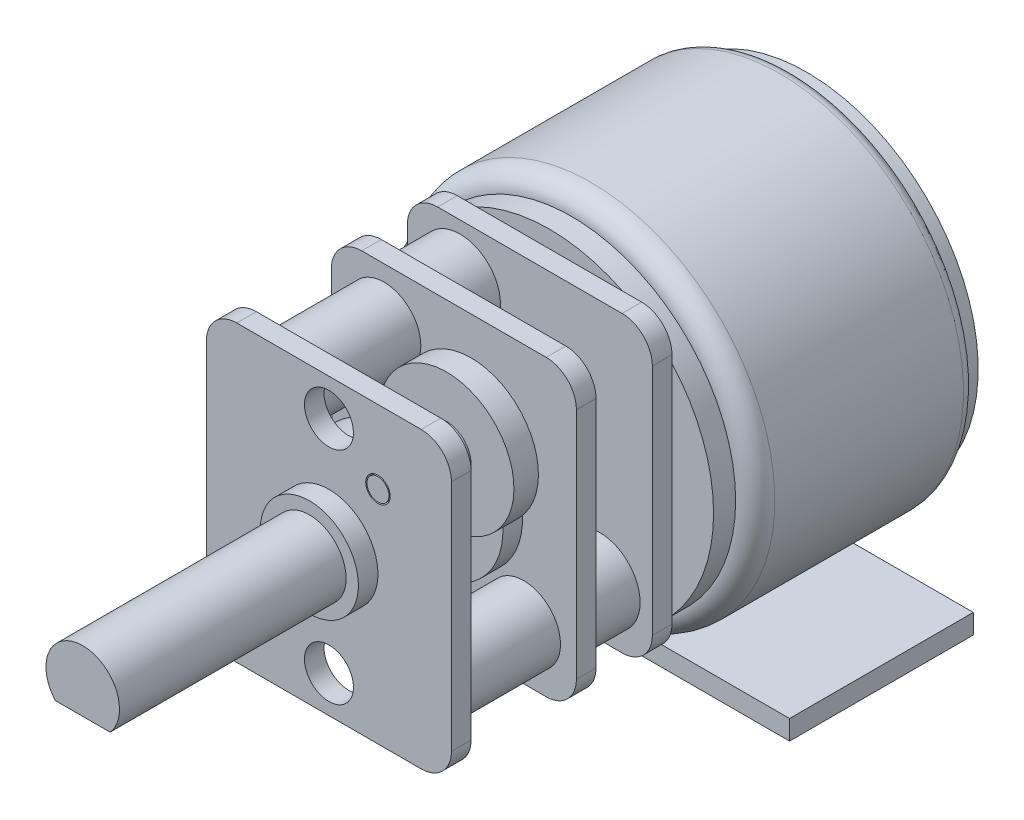
SolidWorks part; units mm, degrees
ref_plane "Front" through (0, 0, 0) normal (0, 0, 1) x (1, 0, 0)
ref_plane "Top" through (0, 0, 0) normal (0, 1, 0) x (1, 0, 0)
ref_plane "Right" through (0, 0, 0) normal (1, 0, 0) x (0, 0, -1)
sketch "Эскиз1" plane through (0, 0, 0) normal (0, 1, 0) x (1, 0, 0)
  line L0 (0, 0) -> (0, -39.2335) construction
  line L1 (0, 0) -> (-0.5, 0)
  line L3 (-0.75, -0.5) -> (-3, -0.5)
  line L4 (-3, -0.5) -> (-3, -1.5)
  line L5 (-3, -1.5) -> (-7, -1.5)
  line L6 (-7, -1.5) -> (-7, -2.1)
  line L8 (-7.5, -2.6) -> (-7.5, -10.3)
  line L10 (-6.7, -11.1) -> (-6.7, -12)
  line L11 (-6.7, -12) -> (-0.75, -12)
  line L12 (0, -12) -> (0, 0)
  line L14 (-7, -2.1) -> (-7, -2.6) construction
  line L15 (-6.7, -11.1) -> (-6.7, -10.3) construction
  line L16 (-6.7, -11.1) -> (-7.5, -11.1) construction
  line L18 (0, -21) -> (-2, -21)
  line L19 (-2, -21) -> (-2, -21.8)
  line L20 (-2, -21.8) -> (-1.5, -21.8)
  line L21 (-1.5, -21.8) -> (-1.5, -31.05)
  line L22 (-1.5, -31.05) -> (0, -31.05)
  line L24 (0, -21) -> (0, -31.05)
  line L25 (-0.75, -12) -> (-0.75, -13.75) construction
  line L26 (0, -14) -> (-0.5, -14) construction
  line L27 (-0.75, -0.5) -> (-0.75, -0.25)
  line L28 (0, -12) -> (-0.75, -12)
  arc A0 (-7, -2.1) -> (-7.5, -2.6) centre (-7, -2.6) ccw
  arc A1 (-7.5, -10.3) -> (-6.7, -11.1) centre (-6.7, -10.3) ccw
  arc A2 (-0.75, -13.75) -> (-0.5, -14) centre (-0.5, -13.75) ccw construction
  arc A3 (-0.5, 0) -> (-0.75, -0.25) centre (-0.5, -0.25) ccw
  dimension "D1" = 6
  dimension "D7" = 0.9
  dimension "D10" = 10.5
  dimension "D16" = 2
  dimension "D4" = 0.5
  dimension "D5" = 0.25
  dimension "D2" = 15
  dimension "D3" = 1
  dimension "D6" = 0.6
  dimension "D8" = 14
  dimension "D9" = 13.4
  dimension "D11" = 19.5
  dimension "D12" = 4
  dimension "D13" = 0.8
  dimension "D14" = 9.25
  dimension "D15" = 3
  dimension "D17" = 1.5
revolve "Motor" add sketch "Эскиз1" angle 360 about L0
sketch "Эскиз2" plane through (0, 0, 31.05) normal (0, 0, 1) x (1, 0, 0)
  line L0 (-1.118, -1) -> (1.118, -1)
  line L1 (-1.6853, 1.5) -> (1.9295, 1.5) construction
  arc A0 (1.118, -1) -> (-1.118, -1) centre (0, 0) ccw
  circle A1 centre (0, 0) radius 1.5 construction
  dimension "D1" = 2.5
extrude "Вырез-Вытянуть2" cut sketch "Эскиз2" against normal up to surface (9.25 mm away) flip side to cut up to face at (-1.5, 0, 21.8)
sketch "Эскиз7" plane through (0, 0, 12) normal (0, 0, 1) x (1, 0, 0)
  line L1 (3.7627, 6) -> (-3.7627, 6)
  line L2 (5, 4.7627) -> (5, -4.7627)
  line L3 (3.7627, -6) -> (-3.7627, -6)
  line L4 (-5, 4.7627) -> (-5, -4.7627)
  line L5 (5, 6) -> (-5, -6) construction
  line L6 (5, -6) -> (-5, 6) construction
  arc A0 (-3.7627, 6) -> (-5, 4.7627) centre (-3.7627, 4.7627) ccw
  arc A1 (-5, -4.7627) -> (-3.7627, -6) centre (-3.7627, -4.7627) ccw
  arc A2 (3.7627, -6) -> (5, -4.7627) centre (3.7627, -4.7627) ccw
  arc A3 (5, 4.7627) -> (3.7627, 6) centre (3.7627, 4.7627) ccw
  point P0 (0, 0)
  point P18 (4.6376, -5.6376)
  point P19 (-4.6376, 5.6376)
  point P20 (0, 0)
  dimension "D3" = 14.6
  dimension "D1" = 10
  dimension "D2" = 12
extrude "Бобышка-Вытянуть5" add sketch "Эскиз7" along normal blind 0.8
sketch "Эскиз8" plane through (0, 0, 21) normal (0, 0, -1) x (-1, 0, 0)
  line L0 (-5, -4.7627) -> (-5, -4.4598) construction
  line L1 (3.7627, 6) -> (-3.7627, 6)
  line L2 (5, 4.7627) -> (5, -4.7627)
  line L3 (3.7627, -6) -> (-3.7627, -6)
  line L4 (-5, 4.7627) -> (-5, -4.7627)
  line L5 (5, 6) -> (-5, -6) construction
  line L6 (5, -6) -> (-5, 6) construction
  line L7 (3.7627, -6) -> (2.9816, -6) construction
  line L8 (0, -4.5) -> (0, 4.5) construction
  line L9 (2, -3) -> (-2, 3) construction
  arc A0 (-3.7627, 6) -> (-5, 4.7627) centre (-3.7627, 4.7627) ccw
  arc A1 (-5, -4.7627) -> (-3.7627, -6) centre (-3.7627, -4.7627) ccw
  arc A2 (3.7627, -6) -> (5, -4.7627) centre (3.7627, -4.7627) ccw
  arc A3 (5, 4.7627) -> (3.7627, 6) centre (3.7627, 4.7627) ccw
  arc A4 (-5, -4.7627) -> (-3.7627, -6) centre (-3.7627, -4.7627) ccw construction
  circle A5 centre (0, -4.5) radius 1
  circle A6 centre (0, 4.5) radius 1
  circle A8 centre (2, -3) radius 0.5
  circle A9 centre (-2, 3) radius 0.5
  point P0 (0, 0)
  point P35 (2, -3)
  point P36 (-2, 3)
  dimension "D3" = 1
  dimension "D1" = 2
  dimension "D2" = 9
  dimension "D4" = 3
  dimension "D5" = 3
extrude "Бобышка-Вытянуть6" add sketch "Эскиз8" along normal blind 0.8
sketch "Эскиз9" plane through (0, 0, 12.8) normal (0, 0, 1) x (1, 0, 0)
  line L0 (4.5, -2.7511) -> (4.5, -4.8531) construction
  line L1 (2.0633, -5.5) -> (3.9242, -5.5) construction
  line L2 (5, -4.7627) -> (5, 4.7627) construction
  line L3 (-3.7627, -6) -> (3.7627, -6) construction
  line L4 (2.85, -3.85) -> (-2.85, 3.85) construction
  circle A0 centre (2.85, -3.85) radius 1.65
  circle A1 centre (-2.85, 3.85) radius 1.65
  point P12 (0, 0)
  point P13 (0, 0)
  point P14 (0, 0)
  dimension "D1" = 3.3
  dimension "D2" = 0.5
  dimension "D3" = 0.5
extrude "Бобышка-Вытянуть7" add sketch "Эскиз9" along normal blind 2.3
sketch "Эскиз10" plane through (0, 0, 15.1) normal (0, 0, 1) x (1, 0, 0)
  line L1 (3.7627, 6) -> (-3.7627, 6)
  line L2 (5, 4.7627) -> (5, -4.7627)
  line L3 (3.7627, -6) -> (1.2373, -6)
  line L4 (-5, 4.7627) -> (-5, -0.2627)
  line L5 (5, 6) -> (-5, -6) construction
  line L6 (5, -6) -> (-5, 6) construction
  line L8 (3.7627, 6) -> (2.9816, 6) construction
  line L9 (5, -4.7627) -> (5, -4.4598) construction
  line L10 (-3.7627, -1.5) -> (-1.2373, -1.5)
  line L11 (0, -4.7627) -> (0, -2.7373)
  arc A0 (-3.7627, 6) -> (-5, 4.7627) centre (-3.7627, 4.7627) ccw
  arc A2 (3.7627, -6) -> (5, -4.7627) centre (3.7627, -4.7627) ccw
  arc A3 (5, 4.7627) -> (3.7627, 6) centre (3.7627, 4.7627) ccw
  arc A4 (5, 4.7627) -> (3.7627, 6) centre (3.7627, 4.7627) ccw construction
  arc A5 (1.2373, -6) -> (0, -4.7627) centre (1.2373, -4.7627) cw
  arc A6 (-5, -0.2627) -> (-3.7627, -1.5) centre (-3.7627, -0.2627) ccw
  arc A7 (0, -2.7373) -> (-1.2373, -1.5) centre (-1.2373, -2.7373) ccw
  point P0 (0, 0)
  point P29 (-0.6647, -4.2471)
  point P32 (0, 0)
  dimension "D1" = 5
  dimension "D2" = 7.5
extrude "Бобышка-Вытянуть8" add sketch "Эскиз10" along normal blind 0.8
sketch "Эскиз11" plane through (0, 0, 15.9) normal (0, 0, 1) x (1, 0, 0)
  circle A0 centre (2.85, -3.85) radius 1.5
  circle A1 centre (-2.85, 3.85) radius 1.5
  circle A4 centre (-2.85, 3.85) radius 1.65 construction
  circle A5 centre (2.85, -3.85) radius 1.65 construction
  dimension "D1" = 3
extrude "Бобышка-Вытянуть9" add sketch "Эскиз11" along normal up to next
sketch "Эскиз12" plane through (0, 0, 0) normal (0, 1, 0) x (1, 0, 0)
  line L0 (0, -20.2) -> (0, -12.8) construction
  line L1 (-1.35, -20.2) -> (-4.35, -20.2) construction
  line L2 (-4.5, -12.8) -> (-1.2, -12.8) construction
  line L3 (0, -20.2) -> (-0.5, -20.2)
  line L4 (-0.5, -20.2) -> (-0.5, -20)
  line L5 (-0.5, -20) -> (-3, -20)
  line L6 (-3, -20) -> (-3, -18.6)
  line L7 (-3, -18.6) -> (-0.5, -18.6)
  line L8 (-0.5, -18.6) -> (-0.5, -18.3)
  line L9 (-0.5, -18.3) -> (-1.5, -18.3)
  line L10 (-1.5, -18.3) -> (-1.5, -16.9)
  line L13 (-1.5, -16.9) -> (-3, -16.9)
  line L14 (-3, -16.9) -> (-3, -16.1)
  line L15 (-3, -16.1) -> (-0.5, -16.1)
  line L16 (-0.5, -16.1) -> (-0.5, -15.9)
  line L17 (-0.5, -15.9) -> (0, -15.9)
  line L18 (0, -15.9) -> (0, -20.2)
  line L19 (-4.35, -15.9) -> (-1.35, -15.9) construction
  line L21 (0, -12.8) -> (-0.75, -12.8)
  line L22 (-0.75, -12.8) -> (-0.75, -13)
  line L23 (-0.75, -13) -> (-1.5, -13)
  line L24 (-1.5, -13) -> (-1.5, -14)
  line L25 (-1.5, -14) -> (-0.75, -14)
  line L26 (-0.75, -14) -> (-0.75, -14.15)
  line L27 (-0.5, -14.4) -> (0, -14.4)
  line L28 (0, -14.4) -> (0, -12.8)
  arc A0 (-0.75, -14.15) -> (-0.5, -14.4) centre (-0.5, -14.15) ccw
  point P3 (-0.5395, -18.1)
  point P16 (-1.5, -16.9349)
  point P32 (-1.4447, -16.9)
  point P34 (-1.5, -16.9)
  point P35 (-1.5, -16.8697)
  dimension "D8" = 1.5
  dimension "D10" = 0.25
  dimension "D1" = 1
  dimension "D2" = 0.2
  dimension "D3" = 1.4
  dimension "D4" = 0.8
  dimension "D5" = 1.4
  dimension "D6" = 3
  dimension "D7" = 6
  dimension "D9" = 1
  dimension "D11" = 3
  dimension "D12" = 1.6
revolve "Повернуть1" add sketch "Эскиз12" angle 360 about L0
ref_plane "Плоскость2" through (0, 0, 0) normal (-0.8321, 0.5547, 0) x (0, 0, 1)
sketch "Эскиз13" plane through (0, 0, 0) normal (-0.8321, 0.5547, 0) x (0, 0, 1)
  line L0 (21, -3.6056) -> (12.8, -3.6056)
  line L1 (12.8, -0.75) -> (12.8, 0.75) construction
  line L2 (21, -3.6056) -> (21, -3.1556)
  line L3 (21, -3.1556) -> (17.3, -3.1556)
  line L4 (17.3, -3.1556) -> (17.3, -2.6056)
  line L5 (17.3, -2.6056) -> (14, -2.6056)
  line L6 (14, -2.6056) -> (14, -0.8556)
  line L7 (14, -0.8556) -> (13, -0.8556)
  line L8 (13, -0.8556) -> (13, -3.305)
  line L9 (13, -3.305) -> (12.8, -3.305)
  line L10 (12.8, -3.305) -> (12.8, -3.6056)
  line L12 (21, -3.6056) -> (22.843, -3.6056) construction
  dimension "D1" = 0.9
  dimension "D2" = 2
  dimension "D3" = 5.5
  dimension "D4" = 0.2
  dimension "D5" = 1
  dimension "D6" = 3.3
revolve "Повернуть2" add sketch "Эскиз13" angle 360 about L12
sketch "Эскиз14" plane through (0, 0, 0) normal (-0.8321, 0.5547, 0) x (0, 0, 1)
  line L0 (21, 3.6056) -> (15.9, 3.6056)
  line L1 (15.9, -0.5) -> (15.9, 0.5) construction
  line L2 (21, 3.6056) -> (21.7209, 3.6056) construction
  line L3 (21, 3.6056) -> (21, 3.1556)
  line L4 (21, 3.1556) -> (20, 3.1556)
  line L5 (20, 3.1556) -> (20, 2.6056)
  line L6 (20, 2.6056) -> (18.2, 2.6056)
  line L7 (18.2, 2.6056) -> (18.2, 0.8556)
  line L8 (18.2, 0.8556) -> (17.2, 0.8556)
  line L9 (17.2, 0.8556) -> (17.2, 3.1056)
  line L10 (17.2, 3.1056) -> (15.9, 3.1056)
  line L11 (15.9, 3.1056) -> (15.9, 3.6056)
  line L12 (20.2, 6.7363) -> (20.2, -1.1893) construction
  line L13 (15.9, -1.1893) -> (15.9, 6.7363) construction
  dimension "D1" = 0.9
  dimension "D2" = 1
  dimension "D3" = 2
  dimension "D4" = 5.5
  dimension "D5" = 0.2
  dimension "D6" = 2
  dimension "D7" = 1.3
revolve "Повернуть3" add sketch "Эскиз14" angle 360 about L2
ref_plane "Плоскость1" through (0, -7.5, 0) normal (0, -1, 0) x (-1, 0, 0)
sketch "Эскиз4" plane through (0, -7.5, 0) normal (0, -1, 0) x (-1, 0, 0)
  line L0 (0, -2.6) -> (0, -10.3) construction
  line L1 (3.5, -10.2) -> (-8, -10.2)
  line L2 (3.5, -10.2) -> (3.5, -2.7)
  line L3 (3.5, -2.7) -> (-8, -2.7)
  line L4 (-8, -10.2) -> (-8, -2.7)
  line L5 (3.5, -6.45) -> (-8, -6.45) construction
  line L7 (7.5, -10.3) -> (-7.5, -10.3) construction
  line L8 (7.5, -2.6) -> (-7.5, -2.6) construction
  point P5 (0, -6.45)
  dimension "D1" = 7.5
  dimension "D2" = 11.5
  dimension "D3" = 3.5
extrude "Плата" add sketch "Эскиз4" along normal blind 0.8 separate body
sketch "Пайка контактов" plane through (0, -8.3, 0) normal (0, -1, 0) x (1, 0, 0)
  line L0 (-0.75, 7.2) -> (2.25, 7.2) construction
  line L1 (0.75, 5.7) -> (-2.25, 5.7) construction
  line L2 (-0.75, 5.7) -> (-0.75, 7.2) construction
  line L3 (-0.75, 6.45) -> (-3.5, 6.45) construction
  line L4 (-3.5, 10.2) -> (-3.5, 2.7) construction
  line L5 (-0.75, 7.2) -> (0.75, 5.7) construction
  line L6 (0, 6.45) -> (0, 0) construction
  line L8 (7, 5.5333) -> (7, 3.7) construction
  line L9 (7, 7.3667) -> (7, 5.5333) construction
  line L10 (7, 7.3667) -> (7, 9.2) construction
  line L11 (7, 6.45) -> (8, 6.45) construction
  line L12 (8, 2.7) -> (8, 10.2) construction
  circle A0 centre (-2.25, 5.7) radius 0.75
  circle A1 centre (-0.75, 7.2) radius 0.75
  circle A2 centre (0.75, 5.7) radius 0.75
  circle A3 centre (2.25, 7.2) radius 0.75
  circle A4 centre (7, 3.7) radius 0.75
  circle A5 centre (7, 5.5333) radius 0.75
  circle A6 centre (7, 7.3667) radius 0.75
  circle A7 centre (7, 9.2) radius 0.75
  point P14 (-3.5, 6.45)
  point P29 (8, 6.45)
  dimension "D1" = 1.5
  dimension "D4" = 1.5
  dimension "D2" = 3
  dimension "D3" = 1.5
  dimension "D5" = 5.5
  dimension "D6" = 1
extrude "Бобышка-Вытянуть3" add sketch "Пайка контактов" along normal blind 0.7 draft 35
sketch "Эскиз6" plane through (0, -8.3, 0) normal (0, -1, 0) x (1, 0, 0)
  line L0 (5.7717, 10.2) -> (5.7717, 2.7) construction
  line L1 (8, 10.2) -> (-3.5, 10.2) construction
  line L2 (-3.5, 2.7) -> (8, 2.7) construction
  line L3 (-3.5, 8.1932) -> (8, 8.1932) construction
  line L4 (-3.5, 10.2) -> (-3.5, 2.7) construction
  line L5 (8, 2.7) -> (8, 10.2) construction
  text T0 "B1 B2 A1 A2" font "Century Gothic" height 0.85
  text T1 " B1 A2 B2 A1" font "Century Gothic" height 0.8
extrude "Бобышка-Вытянуть4" add sketch "Эскиз6" along normal blind 0.01
